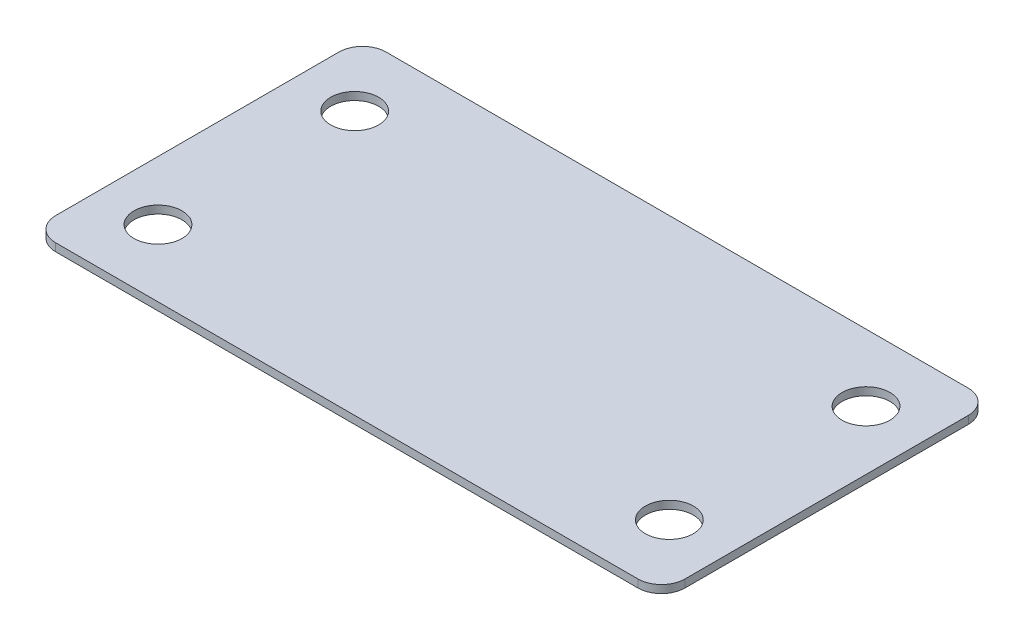
SolidWorks part; units mm, degrees
ref_plane "Спереди" through (0, 0, 0) normal (0, 0, 1) x (1, 0, 0)
ref_plane "Сверху" through (0, 0, 0) normal (0, 1, 0) x (1, 0, 0)
ref_plane "Справа" through (0, 0, 0) normal (1, 0, 0) x (0, 0, -1)
sketch "Эскиз1" plane through (0, 0, 0) normal (0, 1, 0) x (1, 0, 0)
  line L1 (-40, 21) -> (40, 21)
  line L2 (-40, 21) -> (-40, -21)
  line L3 (-40, -21) -> (40, -21)
  line L4 (40, 21) -> (40, -21)
  line L5 (-40, 21) -> (40, -21) construction
  line L6 (-40, -21) -> (40, 21) construction
  point P0 (0, 0)
  dimension "D1" = 80
  dimension "D2" = 42
base flange "Базовая кромка1" sketch "Эскиз1" thickness 1 reverse thickness direction no parameters "D1"=1
fillet "Скругление1" radius 3 4 edges at (40, -0.5, -21) (-40, -0.5, -21) (40, -0.5, 21) (-40, -0.5, 21)
hole_wizard "Диаметр отверстия Ø6.2 (6.2)1" positions "Эскиз2" profile "Эскиз3" hole size "Ø6.2" standard "DIN" end condition through all
sketch "Эскиз2" plane through (0, 0, 0) normal (0, 1, 0) x (1, 0, 0)
  line L1 (-32.5, 12.5) -> (32.5, 12.5)
  line L2 (-32.5, 12.5) -> (-32.5, -12.5)
  line L3 (-32.5, -12.5) -> (32.5, -12.5)
  line L4 (32.5, 12.5) -> (32.5, -12.5)
  line L5 (0, 12.5) -> (0, 21) construction
  line L6 (37, 21) -> (-37, 21) construction
  line L8 (32.5, 0) -> (40, 0) construction
  line L9 (40, -18) -> (40, 18) construction
  point P0 (-32.5, 12.5)
  point P2 (-32.5, -12.5)
  point P4 (32.5, -12.5)
  point P6 (32.5, 12.5)
  point P65 (31.5744, -11.3367)
  dimension "D1" = 65
  dimension "D2" = 25
sketch "Эскиз3" plane through (-32.5, 0, -12.5) normal (1, 0, 0) x (0, 0, 1)
  line L0 (0, 0) -> (0, 1)
  line L1 (0, 1) -> (3.05, 1)
  line L2 (3.05, 1) -> (3.05, 0)
  line L5 (3.05, 0) -> (0, 0)
  line L11 (0, -6.35) -> (0, 107.95) construction
  dimension "Диаметр сквозного отверстия" = 6.1
  dimension "Глубина сквозного отверстия" = 1
sketch "Сгиб-Линии1" [suppressed] plane through (0, 0, 0) normal (0, 1, 0) x (1, 0, 0)
sketch "Граничная рамка1" [suppressed] plane through (0, 0, 0) normal (0, 1, 0) x (1, 0, 0)
sheet metal parameters "Листовой металл1" thickness 1 parameters "D1"=1
flat pattern "Развертка1" [suppressed]
sketch "Сгиб-Линии2" plane through (0, 0, 0) normal (0, 1, 0) x (1, 0, 0)
sketch3d "Граничная рамка2" [suppressed]
  line L0 (-40, -22, 0) -> (40, -22, 0) construction
  line L1 (-40, 22, 0) -> (40, 22, 0) construction
  line L2 (-40, -22, 0) -> (-40, 22, 0) construction
  line L3 (40, -22, 0) -> (40, 22, 0) construction
sheet metal parameters "Листовой металл2" thickness 1 parameters "D1"=1
flat pattern "Развертка1"
sketch "Сгиб-Линии2" plane through (0, 0, 0) normal (0, 1, 0) x (1, 0, 0)
sketch3d "Граничная рамка2" [suppressed]
  line L0 (-40, -21, 0) -> (40, -21, 0) construction
  line L1 (-40, 21, 0) -> (40, 21, 0) construction
  line L2 (-40, -21, 0) -> (-40, 21, 0) construction
  line L3 (40, -21, 0) -> (40, 21, 0) construction
